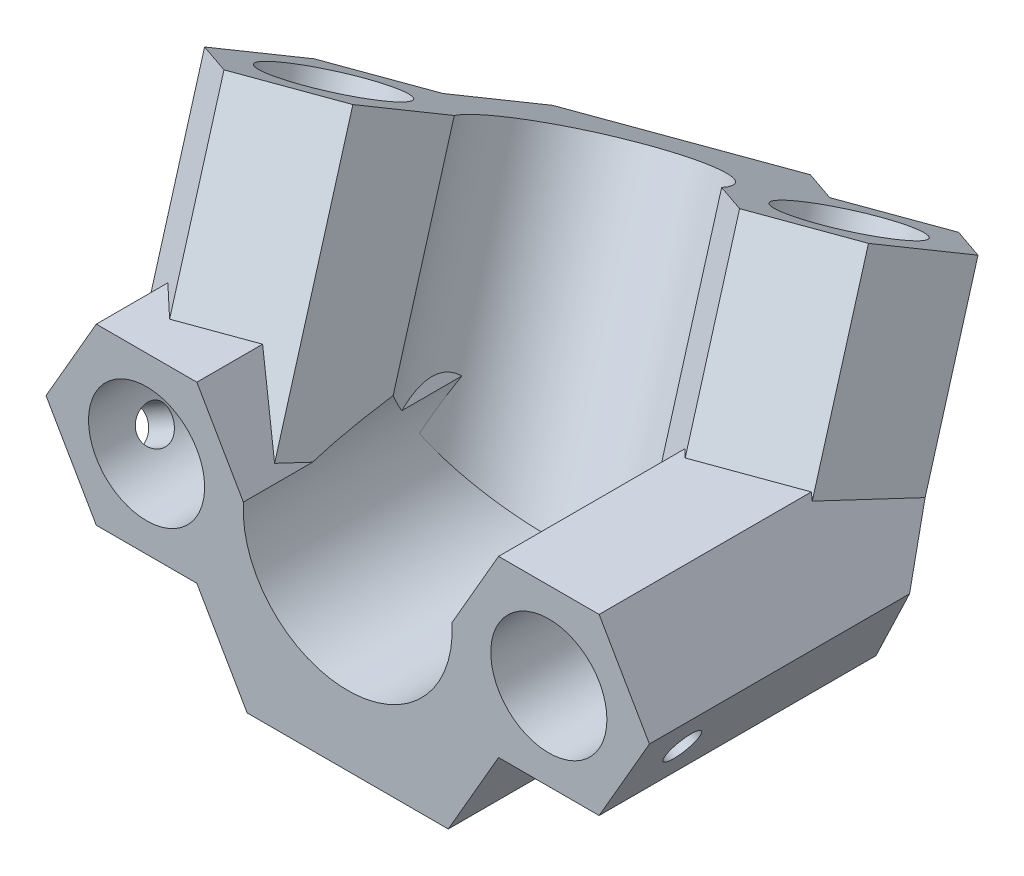
SolidWorks part; units mm, degrees
ref_plane "Front Plane" through (0, 0, 0) normal (0, 0, 1) x (1, 0, 0)
ref_plane "Top Plane" through (0, 0, 0) normal (0, 1, 0) x (1, 0, 0)
ref_plane "Right Plane" through (0, 0, 0) normal (1, 0, 0) x (0, 0, -1)
sketch "Sketch1" plane through (0, 0, 0) normal (0, 1, 0) x (1, 0, 0)
  line L0 (0, 0) -> (0, -10) construction
  line L1 (0, 0) -> (-3.4202, 9.3969) construction
  dimension "D1" = 10
  dimension "D2" = 160
  dimension "D3" = 10
ref_plane "Plane1" through (0, 0, 0) normal (0.9397, 0, -0.342) x (-0.342, 0, -0.9397)
sketch "Sketch2" plane through (0, 0, 0) normal (0.9397, 0, -0.342) x (-0.342, 0, -0.9397)
  line L0 (0, 0) -> (10, 0) construction
  line L1 (0, 0) -> (10, 0) construction
  line L2 (10, 0) -> (10, 17.3205) construction
  line L3 (10, 17.3205) -> (0, 0) construction
  dimension "D1" = 60
  dimension "D2" = 10
sketch "Sketch3" plane through (0, 0, 0) normal (0, 0, 1) x (1, 0, 0)
  line L0 (0, 15) -> (0, -15) construction
  line L1 (12.9904, 7.5) -> (8.6603, 15) construction
  line L2 (8.6603, 15) -> (0, 15) construction
  line L3 (-8.6603, 15) -> (-12.9904, 7.5) construction
  line L4 (-12.9904, -7.5) -> (-8.6603, -15)
  line L5 (-8.6603, -15) -> (8.6603, -15)
  line L6 (8.6603, -15) -> (12.9904, -7.5)
  line L7 (0, 0) -> (17.3205, 0) construction
  line L8 (12.9904, 7.5) -> (10.8253, 3.75) construction
  line L9 (25.9808, 0) -> (21.6506, 7.5)
  line L10 (21.6506, 7.5) -> (12.9904, 7.5)
  line L11 (10.8253, 3.75) -> (8.9827, 0.5584) construction
  line L12 (10.8253, -3.75) -> (12.9904, -7.5) construction
  line L13 (12.9904, -7.5) -> (21.6506, -7.5)
  line L14 (21.6506, -7.5) -> (25.9808, 0)
  line L15 (8.6603, 0) -> (10.8253, -3.75) construction
  line L16 (12.9904, -7.5) -> (13.5705, -6.4952) construction
  line L17 (14.8205, -4.3301) -> (17.3205, 0) construction
  line L18 (13.5705, -6.4952) -> (14.8205, -4.3301) construction
  line L19 (17.3205, 0) -> (14.8205, 4.3301) construction
  line L20 (14.8205, 4.3301) -> (13.5705, 6.4952) construction
  line L21 (13.5705, 6.4952) -> (12.9904, 7.5) construction
  line L22 (-12.9904, -7.5) -> (-21.6506, -7.5)
  line L23 (-21.6506, -7.5) -> (-25.9808, 0)
  line L24 (-25.9808, 0) -> (-21.6506, 7.5)
  line L25 (-21.6506, 7.5) -> (-12.9904, 7.5)
  line L26 (-12.9904, 7.5) -> (-14.8205, 4.3301) construction
  line L27 (-14.8205, 4.3301) -> (-17.3205, 0) construction
  line L28 (-17.3205, 0) -> (-14.8205, -4.3301) construction
  line L29 (-14.8205, -4.3301) -> (-12.9904, -7.5) construction
  line L30 (-17.3205, 7.5) -> (-17.3205, -7.5) construction
  line L31 (-8.9827, 0.5584) -> (-12.9904, 7.5)
  line L32 (8.9827, 0.5584) -> (12.9904, 7.5)
  line L33 (-8.6603, 0) -> (-8.9827, 0.5584) construction
  line L34 (0, 15) -> (-8.6603, 15) construction
  line L35 (8.9827, 0.5584) -> (8.6603, 0) construction
  line L36 (8.6603, 0) -> (8.9827, 0.5584) construction
  circle A0 centre (0, 0) radius 15 construction
  circle A1 centre (17.3205, 0) radius 5
  circle A2 centre (17.3205, 0) radius 7.5 construction
  circle A3 centre (-17.3205, 0) radius 5
  arc A4 (-8.9827, 0.5584) -> (8.9827, 0.5584) centre (0, 0) ccw
  arc A5 (0, 9) -> (-8.9827, 0.5584) centre (0, 0) ccw construction
  arc A6 (8.9827, 0.5584) -> (0, 9) centre (0, 0) ccw construction
  dimension "D2" = 10
  dimension "D4" = 18
  dimension "D1" = 30
  dimension "D3" = 15
extrude "Boss-Extrude1" add sketch "Sketch3" along normal blind 15
ref_plane "Plane2" through (-3.4202, 17.3205, -9.3969) normal (0.171, -0.866, 0.4698) x (-0.9849, -0.1641, 0.056)
sketch "Sketch25" plane through (0, 0, 0) normal (0, 0, -1) x (-1, 0, 0)
  line L0 (-8.9827, 0.5584) -> (-12.9904, 7.5)
  line L1 (-12.9904, 7.5) -> (-21.6506, 7.5)
  line L2 (-21.6506, 7.5) -> (-25.9808, 0)
  line L3 (-25.9808, 0) -> (-21.6506, -7.5)
  line L4 (-21.6506, -7.5) -> (-12.9904, -7.5)
  line L5 (-12.9904, -7.5) -> (-8.6603, -15)
  line L6 (-8.6603, -15) -> (8.6603, -15)
  line L7 (8.6603, -15) -> (12.9904, -7.5)
  line L8 (12.9904, -7.5) -> (21.6506, -7.5)
  line L9 (21.6506, -7.5) -> (25.9808, 0)
  line L10 (25.9808, 0) -> (21.6506, 7.5)
  line L11 (21.6506, 7.5) -> (12.9904, 7.5)
  line L12 (12.9904, 7.5) -> (8.9827, 0.5584)
  arc A0 (-8.9827, 0.5584) -> (8.9827, 0.5584) centre (0, 0) ccw
  arc A1 (-8.9827, 0.5584) -> (8.9827, 0.5584) centre (0, 0) ccw construction
  arc A2 (8.9827, 0.5584) -> (-8.9827, 0.5584) centre (0, 0) ccw construction
sketch "Sketch11" plane through (-3.4202, 17.3205, -9.3969) normal (0.171, -0.866, 0.4698) x (-0.9849, -0.1641, 0.056)
  line L0 (-4.9224, -14.1693) -> (4.9224, 14.1693) construction
  line L7 (13.1031, 11.3274) -> (-3.2583, 17.0113)
  line L20 (-3.2583, 17.0113) -> (-9.8098, 11.3476)
  line L21 (-14.7322, -2.8218) -> (-13.1031, -11.3274) construction
  line L22 (-4.9224, -14.1693) -> (3.2583, -17.0113) construction
  line L23 (3.2583, -17.0113) -> (9.8098, -11.3476) construction
  line L24 (16.3613, -5.6839) -> (15.4208, -0.7732) construction
  line L25 (2.8419, 8.1807) -> (0, 0) construction
  line L26 (-16.3613, 5.6839) -> (16.3613, -5.6839) construction
  line L27 (14.7322, 2.8218) -> (11.4564, -0.0101) construction
  line L28 (-9.8098, 11.3476) -> (-17.9905, 14.1895)
  line L35 (-17.9905, 14.1895) -> (-24.542, 8.5258)
  line L42 (-24.542, 8.5258) -> (-22.9129, 0.0202)
  line L43 (-22.9129, 0.0202) -> (-14.7322, -2.8218)
  line L44 (-14.7322, -2.8218) -> (-8.6685, 2.4202)
  line L45 (-8.302, 3.4752) -> (-8.9952, 7.0948) construction
  line L46 (24.542, -8.5258) -> (22.9129, -0.0202)
  line L47 (22.9129, -0.0202) -> (14.7322, 2.8218)
  line L48 (8.6685, -2.4202) -> (8.1807, -2.8419) construction
  line L49 (8.302, -3.4752) -> (9.8098, -11.3476)
  line L50 (9.8098, -11.3476) -> (17.9905, -14.1895)
  line L51 (17.9905, -14.1895) -> (24.542, -8.5258)
  line L52 (11.4564, -0.0101) -> (8.6685, -2.4202) construction
  line L53 (8.1807, -2.8419) -> (8.302, -3.4752) construction
  line L54 (14.9505, 1.6822) -> (14.7322, 2.8218) construction
  line L55 (14.7322, 2.8218) -> (13.1031, 11.3274)
  line L56 (15.4208, -0.7732) -> (14.9505, 1.6822) construction
  line L57 (12.5788, -8.9538) -> (16.3613, -5.6839) construction
  line L58 (10.6875, -10.5888) -> (12.5788, -8.9538) construction
  line L59 (9.8098, -11.3476) -> (10.6875, -10.5888) construction
  line L60 (-8.9952, 7.0948) -> (-9.8098, 11.3476) construction
  line L61 (-10.6875, 10.5888) -> (-12.5788, 8.9538) construction
  line L62 (-12.5788, 8.9538) -> (-16.3613, 5.6839) construction
  line L63 (-16.3613, 5.6839) -> (-15.4208, 0.7732) construction
  line L64 (-9.8098, 11.3476) -> (-10.6875, 10.5888) construction
  line L65 (-15.4208, 0.7732) -> (-14.9505, -1.6822) construction
  line L66 (-14.9505, -1.6822) -> (-14.7322, -2.8218) construction
  line L67 (-8.6685, 2.4202) -> (-8.1807, 2.8419) construction
  line L68 (-8.1807, 2.8419) -> (-8.302, 3.4752) construction
  line L69 (-13.1031, -11.3274) -> (-4.9224, -14.1693) construction
  circle A0 centre (0, 0) radius 15 construction
  circle A2 centre (-16.3613, 5.6839) radius 7.5 construction
  circle A4 centre (-16.3613, 5.6839) radius 5
  circle A5 centre (16.3613, -5.6839) radius 7.5 construction
  circle A6 centre (16.3613, -5.6839) radius 5
  arc A7 (8.302, -3.4752) -> (-8.6685, 2.4202) centre (0, 0) ccw
  arc A8 (-2.9534, -8.5016) -> (8.302, -3.4752) centre (0, 0) ccw construction
  arc A9 (-8.6685, 2.4202) -> (-2.9534, -8.5016) centre (0, 0) ccw construction
  dimension "D2" = 15
  dimension "D4" = 15
  dimension "D3" = 10
  dimension "D5" = 10
  dimension "D6" = 18
  dimension "D1" = 30
extrude "Boss-Extrude6" add sketch "Sketch11" along normal up to surface (32.9904 mm away) up to face at (0, -15, 7.5)
sketch "Sketch22" plane through (0, 0, 15) normal (0, 0, 1) x (1, 0, 0)
  line L0 (8.6603, -15) -> (-8.6603, -15)
  circle A0 centre (-17.3205, 0) radius 5
  arc A1 (-12.6933, -1.8945) -> (-18.3492, 4.893) centre (-17.3205, 0) ccw construction
  circle A2 centre (17.3205, 0) radius 5
  circle A3 centre (17.3205, 0) radius 5 construction
  circle A4 centre (0, 0) radius 9
  arc A5 (-8.9827, 0.5584) -> (8.9827, 0.5584) centre (0, 0) ccw construction
  arc M23 (8.9827, 0.5584) -> (-8.9827, 0.5584) centre (0, 0) cw
extrude "Cut-Extrude5" cut sketch "Sketch22" against normal up to surface (15 mm away) contours A4 M23 | A0 | A2 region at (0, 0, 15) up to face at (-20.2004, -3.4849, 0)
sketch "Sketch23" plane through (0, 0, 0) normal (0, 1, 0) x (1, 0, 0)
  line L0 (25.9808, -15) -> (25.9808, 0) construction
  line L1 (-25.9808, -15) -> (25.9808, -15)
  line L2 (-25.9808, -15) -> (-25.9808, -23.6809)
  line L3 (-25.9808, -23.6809) -> (25.9808, -23.6809)
  line L4 (25.9808, -15) -> (25.9808, -23.6809)
extrude "Cut-Extrude6" cut sketch "Sketch23" against normal through all both and the other way through all
sketch "Sketch24" plane through (0, 0, 15) normal (0, 0, 1) x (1, 0, 0)
  line L0 (-25.9808, 0) -> (-21.6506, -7.5)
  line L1 (-21.6506, -7.5) -> (-12.9904, -7.5)
  line L2 (-12.9904, -7.5) -> (-8.6603, -15)
  line L3 (-8.6603, -15) -> (-21.219, -15)
  line L4 (-21.219, -15) -> (-25.9808, 0)
  line L5 (8.6603, -15) -> (12.9904, -7.5)
  line L6 (12.9904, -7.5) -> (21.6506, -7.5)
  line L7 (21.6506, -7.5) -> (25.9808, 0)
  line L8 (25.9808, 0) -> (27.3759, -15)
  line L9 (27.3759, -15) -> (8.6603, -15)
extrude "Cut-Extrude7" cut sketch "Sketch24" against normal through all both and the other way through all
extrude "Boss-Extrude7" add sketch "Sketch25" along normal up to surface (22.0446 mm away) up to face at (-6.3157, -3.7874, -13.8064)
sketch "Sketch26" plane through (-3.4202, 17.3205, -9.3969) normal (-0.171, 0.866, -0.4698) x (0.9853, 0.1503, -0.0815)
  line L0 (-12.769, 11.7026) -> (-14.6442, 3.2478)
  line L1 (-14.6442, 3.2478) -> (-25.6176, -0.2111)
  line L2 (-26.8213, -13.1846) -> (-24.8661, 7.8896) construction
  line L3 (-25.6176, -0.2111) -> (-24.8661, 7.8896)
  line L4 (-24.8661, 7.8896) -> (-12.769, 11.7026)
  line L5 (3.7502, 16.9096) -> (10.1348, 11.0583)
  line L6 (10.1348, 11.0583) -> (18.3944, 13.6618)
  line L7 (18.3944, 13.6618) -> (26.2017, 6.5066)
  line L8 (24.3748, -13.1846) -> (27.8723, 24.5131) construction
  line L9 (26.2017, 6.5066) -> (27.8723, 24.5131)
  line L10 (27.8723, 24.5131) -> (3.7502, 16.9096)
extrude "Cut-Extrude8" cut sketch "Sketch26" against normal through all both and the other way through all
sketch "Sketch27" plane through (-19.4856, -11.25, 0) normal (-0.866, -0.5, 0) x (0, 0, 1)
  line L0 (15, 8.6603) -> (1.7562, 8.6603) construction
  line L1 (15, 12.9904) -> (15, 4.3301) construction
  line L2 (0.2402, 12.9904) -> (3.2722, 4.3301) construction
  line L3 (10, 12.9904) -> (10, 4.3301) construction
  line L4 (15, 12.9904) -> (0.2402, 12.9904) construction
  line L5 (15, 4.3301) -> (3.2722, 4.3301) construction
  circle A0 centre (10, 8.6603) radius 1.5
  dimension "D1" = 3
  dimension "D2" = 5
extrude "Cut-Extrude9" cut sketch "Sketch27" against normal up to surface and the other way through all up to face at (-17.3205, 0, 0.3293)
sketch "Sketch28" plane through (19.4856, -11.25, 0) normal (0.866, -0.5, 0) x (0, 0, -1)
  line L0 (-15, 8.6603) -> (8.119, 8.6603) construction
  line L1 (-15, 4.3301) -> (-15, 12.9904) construction
  line L2 (8.8355, 4.3301) -> (7.4025, 12.9904) construction
  circle A0 centre (-10, 8.6603) radius 1.5
  dimension "D1" = 3
  dimension "D2" = 5
extrude "Cut-Extrude10" cut sketch "Sketch28" against normal up to surface (2.7303 mm away) up to face at (22.3205, 0, 0)
sketch "Sketch29" plane through (-21.6427, -5.625, -2.4908) normal (-0.9619, -0.25, -0.1107) x (-0.1071, -0.0278, 0.9939)
  line L0 (-1.8237, 21.7181) -> (5.114, 8.7865) construction
  line L1 (1.992, 23.7651) -> (-5.6394, 19.671) construction
  line L2 (-0.1152, 9.3741) -> (10.3432, 8.1988) construction
  circle A0 centre (0.5401, 17.3121) radius 1.5
  dimension "D1" = 3
  dimension "D2" = 5
extrude "Cut-Extrude11" cut sketch "Sketch29" against normal up to surface (2.5505 mm away) contours A0 up to face at (-19.6962, 14.9362, -7.8678)
sketch "Sketch30" plane through (14.9782, -5.625, -15.8197) normal (0.6657, -0.25, -0.7031) x (-0.7462, -0.223, -0.6272)
  line L0 (-3.8464, 21.4524) -> (-9.6694, -3.2805) construction
  line L1 (0.3685, 20.4601) -> (-8.0613, 22.4447) construction
  line L2 (-8.9416, -4.1065) -> (-14.7444, 2.48) construction
  circle A0 centre (-4.9923, 16.5855) radius 1.5
  dimension "D1" = 3
  dimension "D2" = 5
extrude "Cut-Extrude12" cut sketch "Sketch30" against normal up to surface (2.6834 mm away) up to face at (12.8558, 14.9362, -19.7158)
